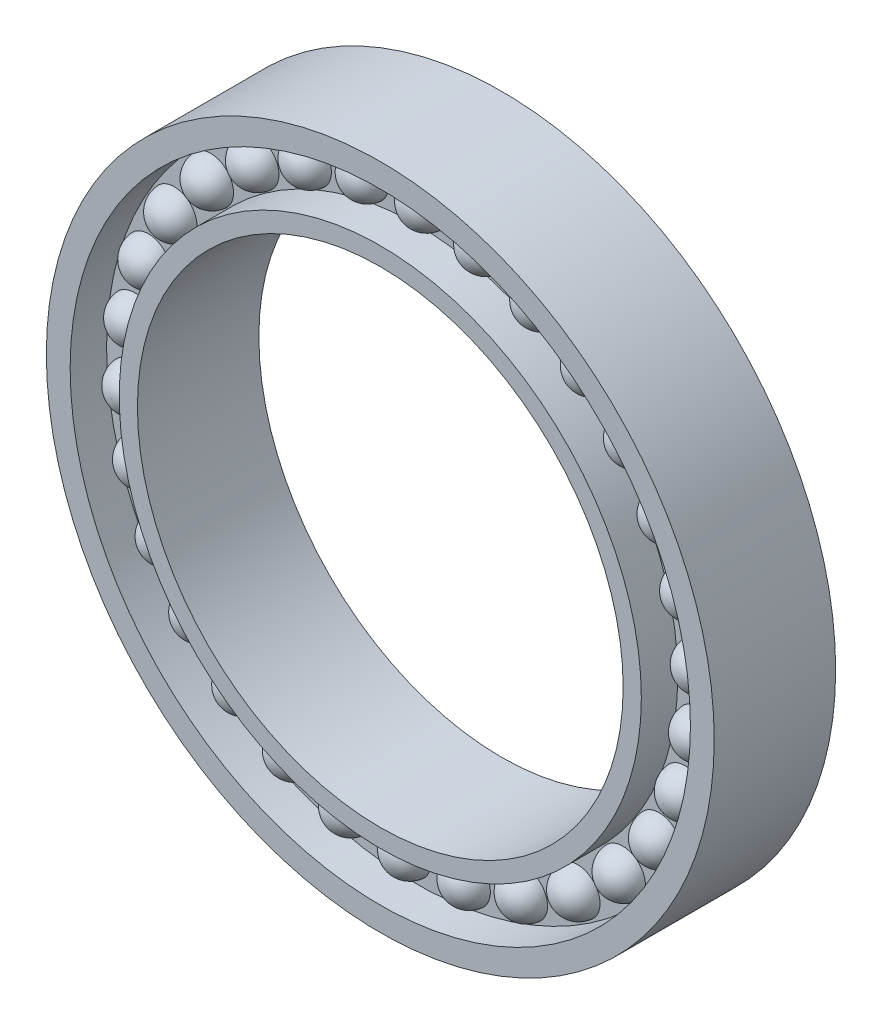
SolidWorks part; units mm, degrees
ref_plane "前视基准面" through (0, 0, 0) normal (0, 0, 1) x (1, 0, 0)
ref_plane "上视基准面" through (0, 0, 0) normal (0, 1, 0) x (1, 0, 0)
ref_plane "右视基准面" through (0, 0, 0) normal (1, 0, 0) x (0, 0, -1)
sketch "草图1" plane through (0, 0, 0) normal (0, 0, 1) x (1, 0, 0)
  circle A0 centre (0, 0) radius 11
  circle A1 centre (0, 0) radius 8
  dimension "D1" = 22
  dimension "D2" = 16
extrude "凸台-拉伸1" add sketch "草图1" along normal mid plane 4
sketch "草图2" plane through (0, 0, 2) normal (0, 0, 1) x (1, 0, 0)
  circle A0 centre (0, 0) radius 8.599
  circle A1 centre (0, 0) radius 10.2158
extrude "切除-拉伸1" cut sketch "草图2" against normal blind 1.2
mirror "镜向1" about plane through (0, 0, 0) normal (0, 0, 1) of "切除-拉伸1"
sketch "草图4" plane through (0, 0, 0) normal (0, 0, 1) x (1, 0, 0)
  circle A0 centre (0.2808, 9.3834) radius 0.75
  dimension "D1" = 1.5
extrude "凸台-拉伸2" add sketch "草图4" along normal mid plane 3
fillet "圆角1" radius 0.75 1 edges at (1.0308, 9.3834, 1.5)
fillet "圆角2" radius 0.75 1 edges at (1.0308, 9.3834, -1.5)
pattern_circular "阵列(圆周)2" count 30 over 360 about axis through (0, 0, 2) along (0, 0, -1) of "凸台-拉伸2", "圆角1", "圆角2"
